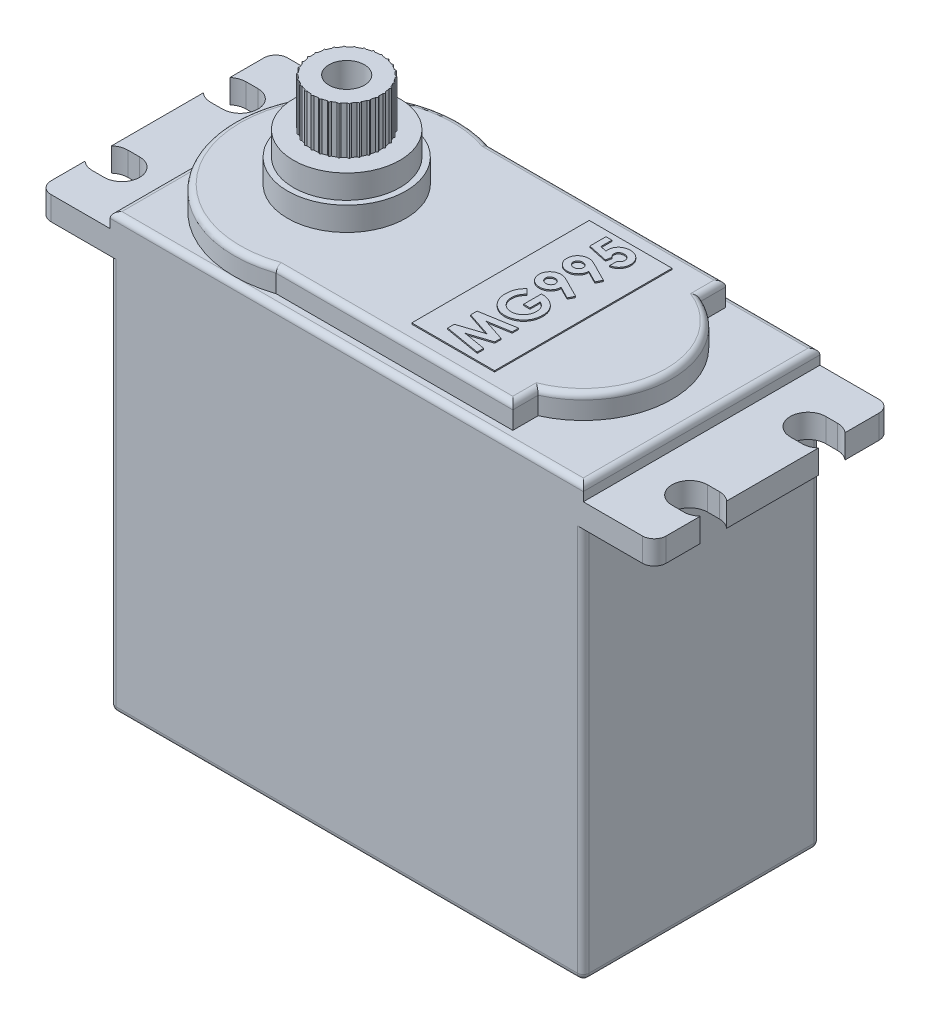
SolidWorks part; units mm, degrees
ref_plane "Front Plane" through (0, 0, 0) normal (0, 0, 1) x (1, 0, 0)
ref_plane "Top Plane" through (0, 0, 0) normal (0, 1, 0) x (1, 0, 0)
ref_plane "Right Plane" through (0, 0, 0) normal (1, 0, 0) x (0, 0, -1)
sketch "Sketch1" plane through (0, 0, 0) normal (0, 1, 0) x (1, 0, 0)
  line L1 (-20, 10) -> (20, 10)
  line L2 (-20, 10) -> (-20, -10)
  line L3 (-20, -10) -> (20, -10)
  line L4 (20, 10) -> (20, -10)
  line L5 (-20, 10) -> (20, -10) construction
  line L6 (-20, -10) -> (20, 10) construction
  point P0 (0, 0)
  dimension "D1" = 20
  dimension "D2" = 40
extrude "Extrude1" add sketch "Sketch1" along normal mid plane 36.5
sketch "Sketch2" plane through (0, 18.25, 0) normal (0, 1, 0) x (1, 0, 0)
  line L0 (13.0414, -6.8557) -> (13.0414, -9)
  line L1 (-6.9586, 9) -> (13.0414, 9)
  line L3 (-6.9586, -9) -> (13.0414, -9)
  line L4 (13.0414, 9) -> (13.0414, 6.8557)
  arc A0 (-6.9586, 9) -> (-6.9586, -9) centre (-10, 0) ccw
  arc A1 (13.0414, -6.8557) -> (13.0414, 6.8557) centre (10, 0) ccw
  dimension "D1" = 19
  dimension "D4" = 15
  dimension "D2" = 10
  dimension "D3" = 18
  dimension "D5" = 20
  dimension "D6" = 10
extrude "Extrude2" add sketch "Sketch2" along normal blind 2
sketch "Sketch3" plane through (0, 20.25, 0) normal (0, 1, 0) x (1, 0, 0)
  circle A0 centre (-10, 0) radius 5
  dimension "D1" = 10
extrude "Extrude3" add sketch "Sketch3" along normal blind 2
sketch "Sketch4" plane through (0, 22.25, 0) normal (0, 1, 0) x (1, 0, 0)
  circle A0 centre (-10, 0) radius 4.5
  dimension "D1" = 9
extrude "Extrude4" add sketch "Sketch4" along normal blind 2
sketch "Sketch5" plane through (0, 24.25, 0) normal (0, 1, 0) x (1, 0, 0)
  line L0 (-10, 0) -> (-10, 3) construction
  line L1 (-10, 3) -> (-10.125, 2.8973)
  line L2 (-10, 3) -> (-9.875, 2.8973)
  line L3 (-9.3763, 2.9344) -> (-9.5199, 2.86)
  line L4 (-9.3763, 2.9344) -> (-9.2753, 2.808)
  line L5 (-8.7798, 2.7406) -> (-8.9358, 2.6977)
  line L6 (-8.7798, 2.7406) -> (-8.7074, 2.596)
  line L7 (-8.2366, 2.4271) -> (-8.3981, 2.4174)
  line L8 (-8.2366, 2.4271) -> (-8.1959, 2.2705)
  line L9 (-7.7706, 2.0074) -> (-7.9305, 2.0316)
  line L10 (-7.7706, 2.0074) -> (-7.7632, 1.8458)
  line L11 (-7.4019, 1.5) -> (-7.5534, 1.5569)
  line L12 (-7.4019, 1.5) -> (-7.4284, 1.3404)
  line L13 (-7.1468, 0.9271) -> (-7.2831, 1.0142)
  line L14 (-7.1468, 0.9271) -> (-7.2059, 0.7764)
  line L15 (-7.0164, 0.3136) -> (-7.1316, 0.4272)
  line L16 (-7.0164, 0.3136) -> (-7.1055, 0.1785)
  line L17 (-7.0164, -0.3136) -> (-7.1055, -0.1785)
  line L18 (-7.0164, -0.3136) -> (-7.1316, -0.4272)
  line L19 (-7.1468, -0.9271) -> (-7.2059, -0.7764)
  line L20 (-7.1468, -0.9271) -> (-7.2831, -1.0142)
  line L21 (-7.4019, -1.5) -> (-7.4284, -1.3404)
  line L22 (-7.4019, -1.5) -> (-7.5534, -1.5569)
  line L23 (-7.7706, -2.0074) -> (-7.7632, -1.8458)
  line L24 (-7.7706, -2.0074) -> (-7.9305, -2.0316)
  line L25 (-8.2366, -2.4271) -> (-8.1959, -2.2705)
  line L26 (-8.2366, -2.4271) -> (-8.3981, -2.4174)
  line L27 (-8.7798, -2.7406) -> (-8.7074, -2.596)
  line L28 (-8.7798, -2.7406) -> (-8.9358, -2.6977)
  line L29 (-9.3763, -2.9344) -> (-9.2753, -2.808)
  line L30 (-9.3763, -2.9344) -> (-9.5199, -2.86)
  line L31 (-10, -3) -> (-9.875, -2.8973)
  line L32 (-10, -3) -> (-10.125, -2.8973)
  line L33 (-10.6237, -2.9344) -> (-10.4801, -2.86)
  line L34 (-10.6237, -2.9344) -> (-10.7247, -2.808)
  line L35 (-11.2202, -2.7406) -> (-11.0642, -2.6977)
  line L36 (-11.2202, -2.7406) -> (-11.2926, -2.596)
  line L37 (-11.7634, -2.4271) -> (-11.6019, -2.4174)
  line L38 (-11.7634, -2.4271) -> (-11.8041, -2.2705)
  line L39 (-12.2294, -2.0074) -> (-12.0695, -2.0316)
  line L40 (-12.2294, -2.0074) -> (-12.2368, -1.8458)
  line L41 (-12.5981, -1.5) -> (-12.4466, -1.5569)
  line L42 (-12.5981, -1.5) -> (-12.5716, -1.3404)
  line L43 (-12.8532, -0.9271) -> (-12.7169, -1.0142)
  line L44 (-12.8532, -0.9271) -> (-12.7941, -0.7764)
  line L45 (-12.9836, -0.3136) -> (-12.8684, -0.4272)
  line L46 (-12.9836, -0.3136) -> (-12.8945, -0.1785)
  line L47 (-12.9836, 0.3136) -> (-12.8945, 0.1785)
  line L48 (-12.9836, 0.3136) -> (-12.8684, 0.4272)
  line L49 (-12.8532, 0.9271) -> (-12.7941, 0.7764)
  line L50 (-12.8532, 0.9271) -> (-12.7169, 1.0142)
  line L51 (-12.5981, 1.5) -> (-12.5716, 1.3404)
  line L52 (-12.5981, 1.5) -> (-12.4466, 1.5569)
  line L53 (-12.2294, 2.0074) -> (-12.2368, 1.8458)
  line L54 (-12.2294, 2.0074) -> (-12.0695, 2.0316)
  line L55 (-11.7634, 2.4271) -> (-11.8041, 2.2705)
  line L56 (-11.7634, 2.4271) -> (-11.6019, 2.4174)
  line L57 (-11.2202, 2.7406) -> (-11.2926, 2.596)
  line L58 (-11.2202, 2.7406) -> (-11.0642, 2.6977)
  line L59 (-10.6237, 2.9344) -> (-10.7247, 2.808)
  line L60 (-10.6237, 2.9344) -> (-10.4801, 2.86)
  arc A0 (-9.875, 2.8973) -> (-10.125, 2.8973) centre (-10, 0) ccw
  circle A1 centre (-10, 0) radius 1.5 construction
  arc A2 (-9.2753, 2.808) -> (-9.5199, 2.86) centre (-10, 0) ccw
  arc A3 (-8.7074, 2.596) -> (-8.9358, 2.6977) centre (-10, 0) ccw
  arc A4 (-8.1959, 2.2705) -> (-8.3981, 2.4174) centre (-10, 0) ccw
  arc A5 (-7.7632, 1.8458) -> (-7.9305, 2.0316) centre (-10, 0) ccw
  arc A6 (-7.4284, 1.3404) -> (-7.5534, 1.5569) centre (-10, 0) ccw
  arc A7 (-7.2059, 0.7764) -> (-7.2831, 1.0142) centre (-10, 0) ccw
  arc A8 (-7.1055, 0.1785) -> (-7.1316, 0.4272) centre (-10, 0) ccw
  arc A9 (-7.1316, -0.4272) -> (-7.1055, -0.1785) centre (-10, 0) ccw
  arc A10 (-7.2831, -1.0142) -> (-7.2059, -0.7764) centre (-10, 0) ccw
  arc A11 (-7.5534, -1.5569) -> (-7.4284, -1.3404) centre (-10, 0) ccw
  arc A12 (-7.9305, -2.0316) -> (-7.7632, -1.8458) centre (-10, 0) ccw
  arc A13 (-8.3981, -2.4174) -> (-8.1959, -2.2705) centre (-10, 0) ccw
  arc A14 (-8.9358, -2.6977) -> (-8.7074, -2.596) centre (-10, 0) ccw
  arc A15 (-9.5199, -2.86) -> (-9.2753, -2.808) centre (-10, 0) ccw
  arc A16 (-10.125, -2.8973) -> (-9.875, -2.8973) centre (-10, 0) ccw
  arc A17 (-10.7247, -2.808) -> (-10.4801, -2.86) centre (-10, 0) ccw
  arc A18 (-11.2926, -2.596) -> (-11.0642, -2.6977) centre (-10, 0) ccw
  arc A19 (-11.8041, -2.2705) -> (-11.6019, -2.4174) centre (-10, 0) ccw
  arc A20 (-12.2368, -1.8458) -> (-12.0695, -2.0316) centre (-10, 0) ccw
  arc A21 (-12.5716, -1.3404) -> (-12.4466, -1.5569) centre (-10, 0) ccw
  arc A22 (-12.7941, -0.7764) -> (-12.7169, -1.0142) centre (-10, 0) ccw
  arc A23 (-12.8945, -0.1785) -> (-12.8684, -0.4272) centre (-10, 0) ccw
  arc A24 (-12.8684, 0.4272) -> (-12.8945, 0.1785) centre (-10, 0) ccw
  arc A25 (-12.7169, 1.0142) -> (-12.7941, 0.7764) centre (-10, 0) ccw
  arc A26 (-12.4466, 1.5569) -> (-12.5716, 1.3404) centre (-10, 0) ccw
  arc A27 (-12.0695, 2.0316) -> (-12.2368, 1.8458) centre (-10, 0) ccw
  arc A28 (-11.6019, 2.4174) -> (-11.8041, 2.2705) centre (-10, 0) ccw
  arc A29 (-11.0642, 2.6977) -> (-11.2926, 2.596) centre (-10, 0) ccw
  arc A30 (-10.4801, 2.86) -> (-10.7247, 2.808) centre (-10, 0) ccw
  dimension "D1" = 5.8
  dimension "D2" = 3
  dimension "D3" = 3
  dimension "D4" = 0.25
extrude "Extrude5" add sketch "Sketch5" along normal blind 4
sketch "Sketch6" plane through (0, 24.25, 0) normal (0, 1, 0) x (1, 0, 0)
  circle A0 centre (-10, 0) radius 2.9
  dimension "D1" = 5.8
extrude "Extrude6" add sketch "Sketch6" along normal blind 4
ref_plane "Plane1" through (0, 15, 0) normal (0, 1, 0) x (-1, 0, 0)
sketch "Sketch7" plane through (0, 15, 0) normal (0, 1, 0) x (-1, 0, 0)
  line L0 (0, 0) -> (0, 15.9425) construction
  line L1 (0, 0) -> (28.4916, 0) construction
  line L2 (20, -10) -> (20, 10) construction
  line L3 (20, 10) -> (26, 10)
  line L4 (20, 10) -> (20, -10)
  line L5 (20, -10) -> (26, -10)
  line L6 (26, 10) -> (26, 6.118)
  line L7 (24, 5) -> (25, 5) construction
  line L8 (24, 3.5) -> (25, 3.5)
  line L9 (24, 6.5) -> (25, 6.5)
  line L10 (24, -5) -> (25, -5) construction
  line L11 (24, -6.5) -> (25, -6.5)
  line L12 (24, -3.5) -> (25, -3.5)
  line L13 (-24, -5) -> (-25, -5) construction
  line L14 (-24, 5) -> (-25, 5) construction
  line L15 (-24, -3.5) -> (-25, -3.5)
  line L16 (-24, -6.5) -> (-25, -6.5)
  line L17 (-24, 6.5) -> (-25, 6.5)
  line L18 (-24, 3.5) -> (-25, 3.5)
  line L19 (-26, 10) -> (-26, 6.118)
  line L20 (-20, -10) -> (-26, -10)
  line L21 (-20, 10) -> (-20, -10)
  line L22 (-20, 10) -> (-26, 10)
  line L23 (26, 3.882) -> (26, -3.882)
  line L24 (26, -6.118) -> (26, -10)
  line L25 (-26, 3.882) -> (-26, -3.882)
  line L26 (-26, -6.118) -> (-26, -10)
  arc A0 (25, 6.5) -> (26, 6.118) centre (25, 5) cw
  arc A1 (24, 6.5) -> (24, 3.5) centre (24, 5) ccw
  arc A2 (24, -6.5) -> (24, -3.5) centre (24, -5) cw
  arc A3 (25, -6.5) -> (26, -6.118) centre (25, -5) ccw
  arc A4 (-25, -6.5) -> (-26, -6.118) centre (-25, -5) cw
  arc A5 (-24, -6.5) -> (-24, -3.5) centre (-24, -5) ccw
  arc A6 (-24, 6.5) -> (-24, 3.5) centre (-24, 5) cw
  arc A7 (-25, 6.5) -> (-26, 6.118) centre (-25, 5) ccw
  arc A8 (26, 3.882) -> (25, 3.5) centre (25, 5) cw
  arc A9 (26, -3.882) -> (25, -3.5) centre (25, -5) ccw
  arc A10 (-26, 3.882) -> (-25, 3.5) centre (-25, 5) ccw
  arc A11 (-26, -3.882) -> (-25, -3.5) centre (-25, -5) cw
  point P1 (24.5, 5)
  dimension "D1" = 24.5
  dimension "D2" = 5
  dimension "D4" = 6
  dimension "D5" = 20
  dimension "D6" = 1
  dimension "D7" = 1.5
extrude "Extrude7" add sketch "Sketch7" along normal blind 2
sketch "Sketch8" plane through (0, 28.25, 0) normal (0, 1, 0) x (1, 0, 0)
  circle A0 centre (-10, 0) radius 1.5
  dimension "D1" = 3
extrude "Extrude8" cut sketch "Sketch8" against normal blind 10
fillet "Fillet4" radius 0.5 6 edges at (17.5, 20.25, 0) (-19.5, 20.25, 0) (3.0414, 20.25, 9) (13.0414, 20.25, -7.9278) (3.0414, 20.25, -9) (13.0414, 20.25, 7.9278)
fillet "Fillet2" radius 0.5 12 edges at (-20, 18.25, 0) (20, 18.25, 0) (0, 18.25, -10) (0, 18.25, 10) (-20, -18.25, 0) (0, -18.25, 10) (20, -18.25, 0) (0, -18.25, -10)
fillet "Fillet3" radius 1 4 edges at (26, 16, 10) (26, 16, -10) (-26, 16, -10) (-26, 16, 10)
sketch "Sketch9" plane through (0, 20.25, 0) normal (0, 1, 0) x (1, 0, 0)
  line L1 (3, 7.5) -> (10, 7.5)
  line L2 (3, 7.5) -> (3, -7.5)
  line L3 (3, -7.5) -> (10, -7.5)
  line L4 (10, 7.5) -> (10, -7.5)
  point P4 (3, 0)
  point P6 (10, 0)
  dimension "D1" = 3
  dimension "D2" = 7
  dimension "D3" = 15
extrude "Extrude9" add sketch "Sketch9" along normal blind 0.1
sketch "Sketch10" plane through (0, 20.35, 0) normal (0, 1, 0) x (1, 0, 0)
  line L0 (8, -8.2) -> (8, 7.5) construction
  text T0 " <b>MG995</b>" font "Century Gothic" height 3
  dimension "D1" = 8
  dimension "D2" = 8.2
extrude "Extrude10" add sketch "Sketch10" along normal blind 0.1
sketch "Sketch12" plane through (0, 18.25, 0) normal (0, 1, 0) x (1, 0, 0)
  circle A0 centre (-10, 0) radius 1.5
  dimension "D1" = 3
extrude "Extrude11" add sketch "Sketch12" against normal blind 37
sketch "Sketch13" plane through (0, 28.25, 0) normal (0, 1, 0) x (1, 0, 0)
  line L60 (-10, 3) -> (-10.125, 2.8973)
  line L61 (-10.4801, 2.86) -> (-10.6237, 2.9344)
  line L62 (-10.6237, 2.9344) -> (-10.7247, 2.808)
  line L63 (-11.0642, 2.6977) -> (-11.2202, 2.7406)
  line L64 (-11.2202, 2.7406) -> (-11.2926, 2.596)
  line L65 (-11.6019, 2.4174) -> (-11.7634, 2.4271)
  line L66 (-11.7634, 2.4271) -> (-11.8041, 2.2705)
  line L67 (-12.0695, 2.0316) -> (-12.2294, 2.0074)
  line L68 (-12.2294, 2.0074) -> (-12.2368, 1.8458)
  line L69 (-12.4466, 1.5569) -> (-12.5981, 1.5)
  line L70 (-12.5981, 1.5) -> (-12.5716, 1.3404)
  line L71 (-12.7169, 1.0142) -> (-12.8532, 0.9271)
  line L72 (-12.8532, 0.9271) -> (-12.7941, 0.7764)
  line L73 (-12.8684, 0.4272) -> (-12.9836, 0.3136)
  line L74 (-12.9836, 0.3136) -> (-12.8945, 0.1785)
  line L75 (-12.8945, -0.1785) -> (-12.9836, -0.3136)
  line L76 (-12.9836, -0.3136) -> (-12.8684, -0.4272)
  line L77 (-12.7941, -0.7764) -> (-12.8532, -0.9271)
  line L78 (-12.8532, -0.9271) -> (-12.7169, -1.0142)
  line L79 (-12.5716, -1.3404) -> (-12.5981, -1.5)
  line L80 (-12.5981, -1.5) -> (-12.4466, -1.5569)
  line L81 (-12.2368, -1.8458) -> (-12.2294, -2.0074)
  line L82 (-12.2294, -2.0074) -> (-12.0695, -2.0316)
  line L83 (-11.8041, -2.2705) -> (-11.7634, -2.4271)
  line L84 (-11.7634, -2.4271) -> (-11.6019, -2.4174)
  line L85 (-11.2926, -2.596) -> (-11.2202, -2.7406)
  line L86 (-11.2202, -2.7406) -> (-11.0642, -2.6977)
  line L87 (-10.7247, -2.808) -> (-10.6237, -2.9344)
  line L88 (-10.6237, -2.9344) -> (-10.4801, -2.86)
  line L89 (-10.125, -2.8973) -> (-10, -3)
  line L90 (-10, -3) -> (-9.875, -2.8973)
  line L91 (-9.5199, -2.86) -> (-9.3763, -2.9344)
  line L92 (-9.3763, -2.9344) -> (-9.2753, -2.808)
  line L93 (-8.9358, -2.6977) -> (-8.7798, -2.7406)
  line L94 (-8.7798, -2.7406) -> (-8.7074, -2.596)
  line L95 (-8.3981, -2.4174) -> (-8.2366, -2.4271)
  line L96 (-8.2366, -2.4271) -> (-8.1959, -2.2705)
  line L97 (-7.9305, -2.0316) -> (-7.7706, -2.0074)
  line L98 (-7.7706, -2.0074) -> (-7.7632, -1.8458)
  line L99 (-7.5534, -1.5569) -> (-7.4019, -1.5)
  line L100 (-7.4019, -1.5) -> (-7.4284, -1.3404)
  line L101 (-7.2831, -1.0142) -> (-7.1468, -0.9271)
  line L102 (-7.1468, -0.9271) -> (-7.2059, -0.7764)
  line L103 (-7.1316, -0.4272) -> (-7.0164, -0.3136)
  line L104 (-7.0164, -0.3136) -> (-7.1055, -0.1785)
  line L105 (-7.1055, 0.1785) -> (-7.0164, 0.3136)
  line L106 (-7.0164, 0.3136) -> (-7.1316, 0.4272)
  line L107 (-7.2059, 0.7764) -> (-7.1468, 0.9271)
  line L108 (-7.1468, 0.9271) -> (-7.2831, 1.0142)
  line L109 (-7.4284, 1.3404) -> (-7.4019, 1.5)
  line L110 (-7.4019, 1.5) -> (-7.5534, 1.5569)
  line L111 (-7.7632, 1.8458) -> (-7.7706, 2.0074)
  line L112 (-7.7706, 2.0074) -> (-7.9305, 2.0316)
  line L113 (-8.1959, 2.2705) -> (-8.2366, 2.4271)
  line L114 (-8.2366, 2.4271) -> (-8.3981, 2.4174)
  line L115 (-8.7074, 2.596) -> (-8.7798, 2.7406)
  line L116 (-8.7798, 2.7406) -> (-8.9358, 2.6977)
  line L117 (-9.2753, 2.808) -> (-9.3763, 2.9344)
  line L118 (-9.3763, 2.9344) -> (-9.5199, 2.86)
  line L119 (-9.875, 2.8973) -> (-10, 3)
  line L120 (-10, 3) -> (-10.125, 2.8973)
  line L121 (-10.4801, 2.86) -> (-10.6237, 2.9344)
  line L122 (-10.6237, 2.9344) -> (-10.7247, 2.808)
  line L123 (-11.0642, 2.6977) -> (-11.2202, 2.7406)
  line L124 (-11.2202, 2.7406) -> (-11.2926, 2.596)
  line L125 (-11.6019, 2.4174) -> (-11.7634, 2.4271)
  line L126 (-11.7634, 2.4271) -> (-11.8041, 2.2705)
  line L127 (-12.0695, 2.0316) -> (-12.2294, 2.0074)
  line L128 (-12.2294, 2.0074) -> (-12.2368, 1.8458)
  line L129 (-12.4466, 1.5569) -> (-12.5981, 1.5)
  line L130 (-12.5981, 1.5) -> (-12.5716, 1.3404)
  line L131 (-12.7169, 1.0142) -> (-12.8532, 0.9271)
  line L132 (-12.8532, 0.9271) -> (-12.7941, 0.7764)
  line L133 (-12.8684, 0.4272) -> (-12.9836, 0.3136)
  line L134 (-12.9836, 0.3136) -> (-12.8945, 0.1785)
  line L135 (-12.8945, -0.1785) -> (-12.9836, -0.3136)
  line L136 (-12.9836, -0.3136) -> (-12.8684, -0.4272)
  line L137 (-12.7941, -0.7764) -> (-12.8532, -0.9271)
  line L138 (-12.8532, -0.9271) -> (-12.7169, -1.0142)
  line L139 (-12.5716, -1.3404) -> (-12.5981, -1.5)
  line L140 (-12.5981, -1.5) -> (-12.4466, -1.5569)
  line L141 (-12.2368, -1.8458) -> (-12.2294, -2.0074)
  line L142 (-12.2294, -2.0074) -> (-12.0695, -2.0316)
  line L143 (-11.8041, -2.2705) -> (-11.7634, -2.4271)
  line L144 (-11.7634, -2.4271) -> (-11.6019, -2.4174)
  line L145 (-11.2926, -2.596) -> (-11.2202, -2.7406)
  line L146 (-11.2202, -2.7406) -> (-11.0642, -2.6977)
  line L147 (-10.7247, -2.808) -> (-10.6237, -2.9344)
  line L148 (-10.6237, -2.9344) -> (-10.4801, -2.86)
  line L149 (-10.125, -2.8973) -> (-10, -3)
  line L150 (-10, -3) -> (-9.875, -2.8973)
  line L151 (-9.5199, -2.86) -> (-9.3763, -2.9344)
  line L152 (-9.3763, -2.9344) -> (-9.2753, -2.808)
  line L153 (-8.9358, -2.6977) -> (-8.7798, -2.7406)
  line L154 (-8.7798, -2.7406) -> (-8.7074, -2.596)
  line L155 (-8.3981, -2.4174) -> (-8.2366, -2.4271)
  line L156 (-8.2366, -2.4271) -> (-8.1959, -2.2705)
  line L157 (-7.9305, -2.0316) -> (-7.7706, -2.0074)
  line L158 (-7.7706, -2.0074) -> (-7.7632, -1.8458)
  line L159 (-7.5534, -1.5569) -> (-7.4019, -1.5)
  line L160 (-7.4019, -1.5) -> (-7.4284, -1.3404)
  line L161 (-7.2831, -1.0142) -> (-7.1468, -0.9271)
  line L162 (-7.1468, -0.9271) -> (-7.2059, -0.7764)
  line L163 (-7.1316, -0.4272) -> (-7.0164, -0.3136)
  line L164 (-7.0164, -0.3136) -> (-7.1055, -0.1785)
  line L165 (-7.1055, 0.1785) -> (-7.0164, 0.3136)
  line L166 (-7.0164, 0.3136) -> (-7.1316, 0.4272)
  line L167 (-7.2059, 0.7764) -> (-7.1468, 0.9271)
  line L168 (-7.1468, 0.9271) -> (-7.2831, 1.0142)
  line L169 (-7.4284, 1.3404) -> (-7.4019, 1.5)
  line L170 (-7.4019, 1.5) -> (-7.5534, 1.5569)
  line L171 (-7.7632, 1.8458) -> (-7.7706, 2.0074)
  line L172 (-7.7706, 2.0074) -> (-7.9305, 2.0316)
  line L173 (-8.1959, 2.2705) -> (-8.2366, 2.4271)
  line L174 (-8.2366, 2.4271) -> (-8.3981, 2.4174)
  line L175 (-8.7074, 2.596) -> (-8.7798, 2.7406)
  line L176 (-8.7798, 2.7406) -> (-8.9358, 2.6977)
  line L177 (-9.2753, 2.808) -> (-9.3763, 2.9344)
  line L178 (-9.3763, 2.9344) -> (-9.5199, 2.86)
  line L179 (-9.875, 2.8973) -> (-10, 3)
  circle A0 centre (-10, 0) radius 1.5 construction
  circle A1 centre (-10, 0) radius 1.5
  arc A30 (-10.125, 2.8973) -> (-10.4801, 2.86) centre (-10, 0) ccw
  arc A31 (-10.7247, 2.808) -> (-11.0642, 2.6977) centre (-10, 0) ccw
  arc A32 (-11.2926, 2.596) -> (-11.6019, 2.4174) centre (-10, 0) ccw
  arc A33 (-11.8041, 2.2705) -> (-12.0695, 2.0316) centre (-10, 0) ccw
  arc A34 (-12.2368, 1.8458) -> (-12.4466, 1.5569) centre (-10, 0) ccw
  arc A35 (-12.5716, 1.3404) -> (-12.7169, 1.0142) centre (-10, 0) ccw
  arc A36 (-12.7941, 0.7764) -> (-12.8684, 0.4272) centre (-10, 0) ccw
  arc A37 (-12.8945, 0.1785) -> (-12.8945, -0.1785) centre (-10, 0) ccw
  arc A38 (-12.8684, -0.4272) -> (-12.7941, -0.7764) centre (-10, 0) ccw
  arc A39 (-12.7169, -1.0142) -> (-12.5716, -1.3404) centre (-10, 0) ccw
  arc A40 (-12.4466, -1.5569) -> (-12.2368, -1.8458) centre (-10, 0) ccw
  arc A41 (-12.0695, -2.0316) -> (-11.8041, -2.2705) centre (-10, 0) ccw
  arc A42 (-11.6019, -2.4174) -> (-11.2926, -2.596) centre (-10, 0) ccw
  arc A43 (-11.0642, -2.6977) -> (-10.7247, -2.808) centre (-10, 0) ccw
  arc A44 (-10.4801, -2.86) -> (-10.125, -2.8973) centre (-10, 0) ccw
  arc A45 (-9.875, -2.8973) -> (-9.5199, -2.86) centre (-10, 0) ccw
  arc A46 (-9.2753, -2.808) -> (-8.9358, -2.6977) centre (-10, 0) ccw
  arc A47 (-8.7074, -2.596) -> (-8.3981, -2.4174) centre (-10, 0) ccw
  arc A48 (-8.1959, -2.2705) -> (-7.9305, -2.0316) centre (-10, 0) ccw
  arc A49 (-7.7632, -1.8458) -> (-7.5534, -1.5569) centre (-10, 0) ccw
  arc A50 (-7.4284, -1.3404) -> (-7.2831, -1.0142) centre (-10, 0) ccw
  arc A51 (-7.2059, -0.7764) -> (-7.1316, -0.4272) centre (-10, 0) ccw
  arc A52 (-7.1055, -0.1785) -> (-7.1055, 0.1785) centre (-10, 0) ccw
  arc A53 (-7.1316, 0.4272) -> (-7.2059, 0.7764) centre (-10, 0) ccw
  arc A54 (-7.2831, 1.0142) -> (-7.4284, 1.3404) centre (-10, 0) ccw
  arc A55 (-7.5534, 1.5569) -> (-7.7632, 1.8458) centre (-10, 0) ccw
  arc A56 (-7.9305, 2.0316) -> (-8.1959, 2.2705) centre (-10, 0) ccw
  arc A57 (-8.3981, 2.4174) -> (-8.7074, 2.596) centre (-10, 0) ccw
  arc A58 (-8.9358, 2.6977) -> (-9.2753, 2.808) centre (-10, 0) ccw
  arc A59 (-9.5199, 2.86) -> (-9.875, 2.8973) centre (-10, 0) ccw
  arc A60 (-10.125, 2.8973) -> (-10.4801, 2.86) centre (-10, 0) ccw
  arc A61 (-10.7247, 2.808) -> (-11.0642, 2.6977) centre (-10, 0) ccw
  arc A62 (-11.2926, 2.596) -> (-11.6019, 2.4174) centre (-10, 0) ccw
  arc A63 (-11.8041, 2.2705) -> (-12.0695, 2.0316) centre (-10, 0) ccw
  arc A64 (-12.2368, 1.8458) -> (-12.4466, 1.5569) centre (-10, 0) ccw
  arc A65 (-12.5716, 1.3404) -> (-12.7169, 1.0142) centre (-10, 0) ccw
  arc A66 (-12.7941, 0.7764) -> (-12.8684, 0.4272) centre (-10, 0) ccw
  arc A67 (-12.8945, 0.1785) -> (-12.8945, -0.1785) centre (-10, 0) ccw
  arc A68 (-12.8684, -0.4272) -> (-12.7941, -0.7764) centre (-10, 0) ccw
  arc A69 (-12.7169, -1.0142) -> (-12.5716, -1.3404) centre (-10, 0) ccw
  arc A70 (-12.4466, -1.5569) -> (-12.2368, -1.8458) centre (-10, 0) ccw
  arc A71 (-12.0695, -2.0316) -> (-11.8041, -2.2705) centre (-10, 0) ccw
  arc A72 (-11.6019, -2.4174) -> (-11.2926, -2.596) centre (-10, 0) ccw
  arc A73 (-11.0642, -2.6977) -> (-10.7247, -2.808) centre (-10, 0) ccw
  arc A74 (-10.4801, -2.86) -> (-10.125, -2.8973) centre (-10, 0) ccw
  arc A75 (-9.875, -2.8973) -> (-9.5199, -2.86) centre (-10, 0) ccw
  arc A76 (-9.2753, -2.808) -> (-8.9358, -2.6977) centre (-10, 0) ccw
  arc A77 (-8.7074, -2.596) -> (-8.3981, -2.4174) centre (-10, 0) ccw
  arc A78 (-8.1959, -2.2705) -> (-7.9305, -2.0316) centre (-10, 0) ccw
  arc A79 (-7.7632, -1.8458) -> (-7.5534, -1.5569) centre (-10, 0) ccw
  arc A80 (-7.4284, -1.3404) -> (-7.2831, -1.0142) centre (-10, 0) ccw
  arc A81 (-7.2059, -0.7764) -> (-7.1316, -0.4272) centre (-10, 0) ccw
  arc A82 (-7.1055, -0.1785) -> (-7.1055, 0.1785) centre (-10, 0) ccw
  arc A83 (-7.1316, 0.4272) -> (-7.2059, 0.7764) centre (-10, 0) ccw
  arc A84 (-7.2831, 1.0142) -> (-7.4284, 1.3404) centre (-10, 0) ccw
  arc A85 (-7.5534, 1.5569) -> (-7.7632, 1.8458) centre (-10, 0) ccw
  arc A86 (-7.9305, 2.0316) -> (-8.1959, 2.2705) centre (-10, 0) ccw
  arc A87 (-8.3981, 2.4174) -> (-8.7074, 2.596) centre (-10, 0) ccw
  arc A88 (-8.9358, 2.6977) -> (-9.2753, 2.808) centre (-10, 0) ccw
  arc A89 (-9.5199, 2.86) -> (-9.875, 2.8973) centre (-10, 0) ccw
  dimension "D1" = 0
